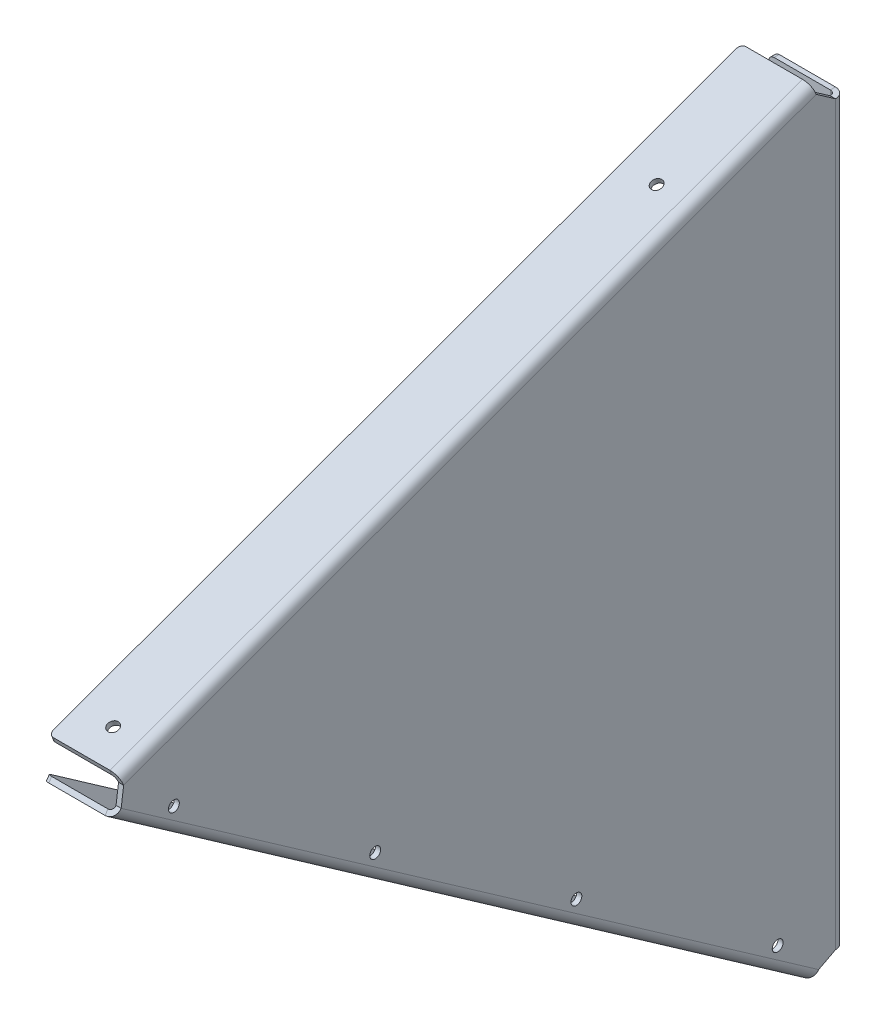
SolidWorks part; units mm, degrees
note: The reader was unsure of these and kept them because the rebuilt part matched: flange length of "Edge-Flange1".
ref_plane "Front Plane" through (0, 0, 0) normal (0, 0, 1) x (1, 0, 0)
ref_plane "Top Plane" through (0, 0, 0) normal (0, 1, 0) x (1, 0, 0)
ref_plane "Right Plane" through (0, 0, 0) normal (1, 0, 0) x (0, 0, -1)
sketch "Sketch1" plane through (0, 0, 0) normal (1, 0, 0) x (0, 0, -1)
  line L0 (0, 12.7) -> (0, 469.9)
  line L1 (-11.9341, 478.2563) -> (-441.5616, 321.8847)
  line L2 (-443.0924, 310.2567) -> (-10.4032, 7.2844)
  line L3 (-441.5616, 321.8847) -> (-443.0924, 310.2567)
  line L4 (0, 469.9) -> (-11.9341, 478.2563)
  line L5 (-10.4032, 7.2844) -> (0, 12.7)
  point P0 (0, 0)
  point P1 (0, 482.6)
  point P4 (-453.4957, 317.5411)
  dimension "D1" = 482.6
  dimension "D2" = 482.6
  dimension "D3" = 70
base flange "Base-Flange1" sketch "Sketch1" thickness 3.175 reverse thickness direction no parameters "D1"=2.032
edge flange "Edge-Flange1" sketch "Sketch16" flange profiles "Sketch16", "Sketch18", "Sketch20" flange angle 90 flange length 41.275 flange position bend outside bend radius 3.175 thickness 3.175 relief rectangular parameters "D6"=10, "D8"=1
bend "EdgeBend4" bend radius 3.175 bend angle 90 parameters "D5"=1
bend "EdgeBend5" bend radius 3.175 bend angle 90 parameters "D5"=2
bend "EdgeBend6" bend radius 3.175 bend angle 90 parameters "D5"=3
sketch "Sketch16" plane through (-3.175, 0, 0) normal (0, -0.8192, 0.5736) x (0, 0.5736, 0.8192)
  line L0 (540.916, 0) -> (12.7, 0) construction
  line L1 (540.916, 0) -> (12.7, 0)
  line L2 (12.7, 0) -> (12.7, 41.275)
  line L3 (12.7, 41.275) -> (540.916, 41.275)
  line L4 (540.916, 41.275) -> (540.916, 0)
sketch "Sketch18" plane through (-3.175, 0, 0) normal (0, 0, -1) x (0, -1, 0)
  line L0 (-12.7, 0) -> (-469.9, 0) construction
  line L1 (-12.7, 0) -> (-469.9, 0)
  line L2 (-469.9, 0) -> (-469.9, 41.275)
  line L3 (-469.9, 41.275) -> (-12.7, 41.275)
  line L4 (-12.7, 41.275) -> (-12.7, 0)
sketch "Sketch20" plane through (-3.175, 426.1465, 155.1047) normal (0, 0.9397, 0.342) x (0, 0.342, -0.9397)
  line L0 (152.3589, 0) -> (-304.8411, 0) construction
  line L1 (152.3589, 0) -> (-304.8411, 0)
  line L2 (-304.8411, 0) -> (-304.8411, 41.275)
  line L3 (-304.8411, 41.275) -> (152.3589, 41.275)
  line L4 (152.3589, 41.275) -> (152.3589, 0)
sketch "Sketch21" plane through (0, 0, -6.35) normal (0, 0, -1) x (-1, 0, 0)
  line L0 (44.45, 12.7) -> (44.45, 469.9) construction
  line L1 (6.35, 12.7) -> (44.45, 12.7) construction
  point P0 (22.225, 390.525)
  point P1 (22.225, 31.75)
  dimension "D1" = 22.225
  dimension "D2" = 358.775
  dimension "D3" = 19.05
hole_wizard "17/64 (0.26563) Diameter Hole1" positions "Sketch23" profile "Sketch24" hole size "17/64" standard "ANSI Inch"
sketch "Sketch23" plane through (0, 0, -6.35) normal (0, 0, -1) x (-1, 0, 0)
  point P0 (22.225, 390.525)
  point P3 (22.225, 31.75)
sketch "Sketch24" plane through (-22.225, 390.525, -6.35) normal (1, 0, 0) x (0, 1, 0)
  line L0 (0, 0) -> (0, 5.202)
  line L1 (0, 5.202) -> (3.3735, 3.175)
  line L2 (3.3735, 3.175) -> (3.3735, 0)
  line L5 (3.3735, 0) -> (0, 0)
  line L10 (0, 5.202) -> (-3.3735, 3.175) construction
  line L11 (0, -6.35) -> (0, 107.95) construction
  dimension "Hole Dia." = 6.747
  dimension "Hole Depth" = 3.175
  dimension "Drill Angle" = 118
sketch "Sketch26" plane through (0, 432.1136, 157.2765) normal (0, 0.9397, 0.342) x (1, 0, 0)
  line L0 (-44.45, 152.3589) -> (-44.45, -304.8411) construction
  line L1 (-44.45, -304.8411) -> (-6.35, -304.8411) construction
  point P0 (-22.225, -285.7911)
  point P1 (-22.225, 72.9839)
  dimension "D1" = 22.225
  dimension "D2" = 19.05
  dimension "D3" = 358.775
hole_wizard "17/64 (0.26563) Diameter Hole2" positions "Sketch27" profile "Sketch28" hole size "17/64" standard "ANSI Inch"
sketch "Sketch27" plane through (0, 432.1136, 157.2765) normal (0, 0.9397, 0.342) x (1, 0, 0)
  point P0 (-22.225, 72.9839)
  point P3 (-22.225, -285.7911)
sketch "Sketch28" plane through (-22.225, 457.0755, 88.694) normal (1, 0, 0) x (0, -0.342, 0.9397)
  line L0 (0, 0) -> (0, 5.202)
  line L1 (0, 5.202) -> (3.3735, 3.175)
  line L2 (3.3735, 3.175) -> (3.3735, 0)
  line L5 (3.3735, 0) -> (0, 0)
  line L10 (0, 5.202) -> (-3.3735, 3.175) construction
  line L11 (0, -6.35) -> (0, 107.95) construction
  dimension "Hole Dia." = 6.747
  dimension "Hole Depth" = 3.175
  dimension "Drill Angle" = 118
fillet "Fillet1" radius 3.175 6 edges at (-44.45, 306.3554, 445.8241) (-44.45, 326.36, 443.1904) (-44.45, 482.7316, 13.563) (-44.45, 469.9, -4.7625) (-44.45, 3.3832, 13.1349) (-44.45, 12.7, -4.7625)
sketch "Sketch30" plane through (0, -5.2016, 3.6422) normal (0, -0.8192, 0.5736) x (1, 0, 0)
  line L1 (-44.45, 537.741) -> (-44.45, 15.875) construction
  point P0 (-22.225, 505.408)
  point P1 (-22.225, 353.008)
  point P2 (-22.225, 200.608)
  point P3 (-22.225, 48.208)
  point P4 (-44.45, 276.808)
  dimension "D1" = 152.4
  dimension "D2" = 152.4
  dimension "D4" = 152.4
  dimension "D5" = 22.225
  dimension "D3" = 76.2
hole_wizard "17/64 (0.26563) Diameter Hole3" positions "Sketch31" profile "Sketch32" hole size "17/64" standard "ANSI Inch"
sketch "Sketch31" plane through (0, -5.2016, 3.6422) normal (0, -0.8192, 0.5736) x (-1, 0, 0)
  point P0 (22.225, -48.208)
  point P3 (22.225, -200.608)
  point P6 (22.225, -353.008)
  point P9 (22.225, -505.408)
sketch "Sketch32" plane through (-22.225, 22.4494, 43.1319) normal (1, 0, 0) x (0, -0.5736, -0.8192)
  line L0 (0, 0) -> (0, 5.202)
  line L1 (0, 5.202) -> (3.3735, 3.175)
  line L2 (3.3735, 3.175) -> (3.3735, 0)
  line L5 (3.3735, 0) -> (0, 0)
  line L10 (0, 5.202) -> (-3.3735, 3.175) construction
  line L11 (0, -6.35) -> (0, 107.95) construction
  dimension "Hole Dia." = 6.747
  dimension "Hole Depth" = 3.175
  dimension "Drill Angle" = 118
sketch "Sketch33" plane through (0, 0, 0) normal (1, 0, 0) x (0, 0, -1)
  line L0 (-410.3638, 295.0917) -> (-35.8475, 32.8526) construction
  line L1 (-443.0924, 310.2567) -> (-10.4032, 7.2844) construction
  line L2 (-446.7346, 305.055) -> (-14.0454, 2.0828) construction
  line L3 (-223.1056, 163.9722) -> (-230.39, 153.5689) construction
  point P2 (-160.6862, 120.2656)
  point P5 (-285.525, 207.6787)
  point P8 (-223.1056, 163.9722)
  point P9 (-230.39, 153.5689)
  dimension "D1" = 12.7
  dimension "D2" = 152.4
  dimension "D3" = 152.4
  dimension "D4" = 152.4
hole_wizard "17/64 (0.26563) Diameter Hole4" positions "Sketch34" profile "Sketch36" hole size "17/64" standard "ANSI Inch" end condition through all
sketch "Sketch34" plane through (0, 0, 0) normal (1, 0, 0) x (0, 0, -1)
  point P0 (-410.3638, 295.0917)
  point P3 (-285.525, 207.6787)
  point P6 (-160.6862, 120.2656)
  point P9 (-35.8475, 32.8526)
sketch "Sketch36" plane through (0, 295.0917, 410.3638) normal (0, 1, 0) x (0, 0, -1)
  line L0 (0, 0) -> (0, 44.45)
  line L1 (0, 44.45) -> (3.3735, 44.45)
  line L2 (3.3735, 44.45) -> (3.3735, 0)
  line L5 (3.3735, 0) -> (0, 0)
  line L11 (0, -6.35) -> (0, 107.95) construction
  dimension "Thru Hole Dia." = 6.747
  dimension "Thru Hole Depth" = 44.45
sketch "Bend-Lines1" [suppressed] plane through (0, 0, 0) normal (0, 1, 0) x (1, 0, 0)
sketch "Bounding-Box1" [suppressed] plane through (0, 0, 0) normal (0, 1, 0) x (1, 0, 0)
sheet metal parameters "Sheet-Metal1" thickness 3.175 parameters "D1"=2.032
flat pattern "Flat-Pattern1" [suppressed]
sketch "Bend-Lines2" plane through (0, 0, 0) normal (0, 1, 0) x (1, 0, 0)
sketch3d "Bounding-Box2" [suppressed]
  line L0 (-215.9, 644.525, 0) -> (212.725, 215.9, 0) construction
  line L1 (-430.2125, 430.2125, 0) -> (-1.5875, 1.5875, 0) construction
  line L2 (-215.9, 644.525, 0) -> (-430.2125, 430.2125, 0) construction
  line L3 (212.725, 215.9, 0) -> (-1.5875, 1.5875, 0) construction
sheet metal parameters "Sheet-Metal2" thickness 3.175 parameters "D1"=2.032
flat pattern "Flat-Pattern1" [suppressed]
sketch "Bend-Lines2" plane through (0, 0, 0) normal (1, 0, 0) x (0, 0, -1)
  line L6 (-4.0349, 485.3913) -> (-464.0571, 362.1287) construction
  line L7 (3.7405, 3.175) -> (3.7405, 479.425) construction
  line L8 (-465.914, 352.7936) -> (-4.7959, -1.0347) construction
  line L9 (-4.0349, 485.3913) -> (-464.0571, 362.1287) construction
  line L10 (3.7405, 3.175) -> (3.7405, 479.425) construction
  line L11 (-465.914, 352.7936) -> (-4.7959, -1.0347) construction
sketch3d "Bounding-Box2" [suppressed]
  line L0 (-244.8751, 702.2997, 0) -> (275.592, 302.9313, 0) construction
  line L1 (-521.0594, 342.3694, 0) -> (-0.5922, -56.999, 0) construction
  line L2 (-244.8751, 702.2997, 0) -> (-521.0594, 342.3694, 0) construction
  line L3 (275.592, 302.9313, 0) -> (-0.5922, -56.999, 0) construction
bend of the flat pattern "Flatten-<EdgeBend4>1"
bend of the flat pattern "Flatten-<EdgeBend5>1"
bend of the flat pattern "Flatten-<EdgeBend6>1"
sketch "Sketch21-1" [suppressed] plane through (0, 0, -1.1309) normal (1, 0, 0) x (0, 0, -1)
  line L0 (44.45, 3.175) -> (44.45, 479.425) construction
  line L1 (-1.1309, 3.175) -> (44.45, 3.175) construction
  point P0 (22.225, 447.675)
  point P1 (22.225, 41.275)
  dimension "D1" = 22.225
  dimension "D2" = 406.4
  dimension "D3" = 38.1
sheet metal parameters "Sheet-Metal3" thickness 3.175 parameters "D1"=2.032
flat pattern "Flat-Pattern1" [suppressed]
sketch "Bend-Lines2" plane through (0, 0, 0) normal (1, 0, 0) x (0, 0, -1)
  line L6 (-4.0349, 485.3913) -> (-464.0571, 362.1287) construction
  line L7 (3.7405, 3.175) -> (3.7405, 479.425) construction
  line L8 (-465.914, 352.7936) -> (-4.7959, -1.0347) construction
  line L9 (-4.0349, 485.3913) -> (-464.0571, 362.1287) construction
  line L10 (3.7405, 3.175) -> (3.7405, 479.425) construction
  line L11 (-465.914, 352.7936) -> (-4.7959, -1.0347) construction
sketch3d "Bounding-Box2" [suppressed]
  line L0 (-244.8751, 702.2997, 0) -> (275.592, 302.9313, 0) construction
  line L1 (-521.0594, 342.3694, 0) -> (-0.5922, -56.999, 0) construction
  line L2 (-244.8751, 702.2997, 0) -> (-521.0594, 342.3694, 0) construction
  line L3 (275.592, 302.9313, 0) -> (-0.5922, -56.999, 0) construction
bend of the flat pattern "Flatten-<EdgeBend4>1"
bend of the flat pattern "Flatten-<EdgeBend5>1"
bend of the flat pattern "Flatten-<EdgeBend6>1"
sketch "Sketch21-1" [suppressed] plane through (0, 0, -1.1309) normal (1, 0, 0) x (0, 0, -1)
  line L0 (44.45, 3.175) -> (44.45, 479.425) construction
  line L1 (-1.1309, 3.175) -> (44.45, 3.175) construction
  point P0 (22.225, 400.05)
  point P1 (22.225, 41.275)
  dimension "D1" = 22.225
  dimension "D2" = 358.775
  dimension "D3" = 38.1
sheet metal parameters "Sheet-Metal4" thickness 3.175 parameters "D1"=2.032
flat pattern "Flat-Pattern1" [suppressed]
sketch "Bend-Lines2" plane through (0, 0, 0) normal (1, 0, 0) x (0, 0, -1)
  line L6 (-4.0349, 485.3913) -> (-464.0571, 362.1287) construction
  line L7 (3.7405, 3.175) -> (3.7405, 479.425) construction
  line L8 (-465.914, 352.7936) -> (-4.7959, -1.0347) construction
  line L9 (-4.0349, 485.3913) -> (-464.0571, 362.1287) construction
  line L10 (3.7405, 3.175) -> (3.7405, 479.425) construction
  line L11 (-465.914, 352.7936) -> (-4.7959, -1.0347) construction
sketch3d "Bounding-Box2" [suppressed]
  line L0 (-244.6392, 700.5096, 0) -> (273.8019, 302.6955, 0) construction
  line L1 (-520.0463, 341.5923, 0) -> (-1.6052, -56.2218, 0) construction
  line L2 (-244.6392, 700.5096, 0) -> (-520.0463, 341.5923, 0) construction
  line L3 (273.8019, 302.6955, 0) -> (-1.6052, -56.2218, 0) construction
bend of the flat pattern "Flatten-<EdgeBend4>1"
bend of the flat pattern "Flatten-<EdgeBend5>1"
bend of the flat pattern "Flatten-<EdgeBend6>1"
sketch "Sketch21-1" plane through (0, 0, -1.1309) normal (1, 0, 0) x (0, 0, -1)
  line L0 (44.45, 6.35) -> (44.45, 476.25) construction
  line L1 (-1.1309, 3.175) -> (41.275, 3.175) construction
  point P0 (22.225, 390.525)
  point P1 (22.225, 31.75)
  dimension "D1" = 22.225
  dimension "D2" = 358.775
  dimension "D3" = 28.575
sketch "Sketch26-1" [suppressed] plane through (0, 451.3643, 120.9427) normal (1, 0, 0) x (0, -0.9659, -0.2588)
  line L0 (-44.45, 118.5561) -> (-44.45, -351.3439) construction
  line L1 (-41.275, -354.5189) -> (1.1309, -354.5189) construction
  point P0 (-22.225, -325.9439)
  point P1 (-22.225, 32.8311)
  dimension "D1" = 22.225
  dimension "D2" = 28.575
  dimension "D3" = 358.775
sheet metal parameters "Sheet-Metal5" thickness 3.175 parameters "D1"=2.032
flat pattern "Flat-Pattern1" [suppressed]
sketch "Bend-Lines2" plane through (0, 0, 0) normal (1, 0, 0) x (0, 0, -1)
  line L6 (-13.2134, 481.7712) -> (-442.8409, 325.3996) construction
  line L7 (3.7405, 12.7) -> (3.7405, 469.9) construction
  line L8 (-445.2379, 307.1927) -> (-12.5487, 4.2204) construction
  line L9 (-13.2134, 481.7712) -> (-442.8409, 325.3996) construction
  line L10 (3.7405, 12.7) -> (3.7405, 469.9) construction
  line L11 (-445.2379, 307.1927) -> (-12.5487, 4.2204) construction
sketch3d "Bounding-Box2" [suppressed]
  line L0 (-242.03, 669.7656, 0) -> (258.6579, 319.1783, 0) construction
  line L1 (-503.2365, 296.7261, 0) -> (-2.5487, -53.8612, 0) construction
  line L2 (-242.03, 669.7656, 0) -> (-503.2365, 296.7261, 0) construction
  line L3 (258.6579, 319.1783, 0) -> (-2.5487, -53.8612, 0) construction
bend of the flat pattern "Flatten-<EdgeBend4>1"
bend of the flat pattern "Flatten-<EdgeBend5>1"
bend of the flat pattern "Flatten-<EdgeBend6>1"
sketch "Sketch21-1" plane through (0, 0, -1.1309) normal (1, 0, 0) x (0, 0, -1)
  line L0 (44.45, 15.875) -> (44.45, 466.725) construction
  line L1 (-1.1309, 12.7) -> (41.275, 12.7) construction
  point P0 (22.225, 390.525)
  point P1 (22.225, 31.75)
  dimension "D1" = 22.225
  dimension "D2" = 358.775
  dimension "D3" = 19.05
sketch "Sketch26-1" plane through (0, 427.2092, 155.4914) normal (1, 0, 0) x (0, -0.9397, -0.342)
  line L0 (-44.45, 149.1839) -> (-44.45, -301.6661) construction
  line L1 (-41.275, -304.8411) -> (1.1309, -304.8411) construction
  point P0 (-22.225, -285.7911)
  point P1 (-22.225, 72.9839)
  dimension "D1" = 22.225
  dimension "D2" = 19.05
  dimension "D3" = 358.775
sketch "Sketch30-1" plane through (0, -0.9264, 0.6487) normal (1, 0, 0) x (0, 0.8192, -0.5736)
  line L1 (-44.45, 537.741) -> (-44.45, 15.875) construction
  point P0 (-22.225, 505.408)
  point P1 (-22.225, 353.008)
  point P2 (-22.225, 200.608)
  point P3 (-22.225, 48.208)
  point P4 (-44.45, 276.808)
  dimension "D1" = 152.4
  dimension "D2" = 152.4
  dimension "D3" = 76.2
  dimension "D4" = 152.4
  dimension "D5" = 22.225
sheet metal parameters "Sheet-Metal6" thickness 3.175 parameters "D1"=2.032
flat pattern "Flat-Pattern1" [suppressed]
sketch "Bend-Lines2" plane through (0, 0, 0) normal (1, 0, 0) x (0, 0, -1)
  line L6 (-13.2134, 481.7712) -> (-442.8409, 325.3996) construction
  line L7 (3.7405, 12.7) -> (3.7405, 469.9) construction
  line L8 (-445.2379, 307.1927) -> (-12.5487, 4.2204) construction
  line L9 (-13.2134, 481.7712) -> (-442.8409, 325.3996) construction
  line L10 (3.7405, 12.7) -> (3.7405, 469.9) construction
  line L11 (-445.2379, 307.1927) -> (-12.5487, 4.2204) construction
sketch3d "Bounding-Box2" [suppressed]
  line L0 (-242.03, 669.7656, 0) -> (258.6579, 319.1783, 0) construction
  line L1 (-503.2365, 296.7261, 0) -> (-2.5487, -53.8612, 0) construction
  line L2 (-242.03, 669.7656, 0) -> (-503.2365, 296.7261, 0) construction
  line L3 (258.6579, 319.1783, 0) -> (-2.5487, -53.8612, 0) construction
bend of the flat pattern "Flatten-<EdgeBend4>1"
bend of the flat pattern "Flatten-<EdgeBend5>1"
bend of the flat pattern "Flatten-<EdgeBend6>1"
sketch "Sketch21-1" plane through (0, 0, -1.1309) normal (1, 0, 0) x (0, 0, -1)
  line L0 (44.45, 15.875) -> (44.45, 466.725) construction
  line L1 (-1.1309, 12.7) -> (41.275, 12.7) construction
  point P0 (22.225, 390.525)
  point P1 (22.225, 31.75)
  dimension "D1" = 22.225
  dimension "D2" = 358.775
  dimension "D3" = 19.05
sketch "Sketch26-1" plane through (0, 427.2092, 155.4914) normal (1, 0, 0) x (0, -0.9397, -0.342)
  line L0 (-44.45, 149.1839) -> (-44.45, -301.6661) construction
  line L1 (-41.275, -304.8411) -> (1.1309, -304.8411) construction
  point P0 (-22.225, -285.7911)
  point P1 (-22.225, 72.9839)
  dimension "D1" = 22.225
  dimension "D2" = 19.05
  dimension "D3" = 358.775
sketch "Sketch30-1" plane through (0, -0.9264, 0.6487) normal (1, 0, 0) x (0, 0.8192, -0.5736)
  line L1 (-44.45, 537.741) -> (-44.45, 15.875) construction
  point P0 (-22.225, 505.408)
  point P1 (-22.225, 353.008)
  point P2 (-22.225, 200.608)
  point P3 (-22.225, 48.208)
  point P4 (-44.45, 276.808)
  dimension "D1" = 152.4
  dimension "D2" = 152.4
  dimension "D3" = 76.2
  dimension "D4" = 152.4
  dimension "D5" = 22.225
equation "\"D2@Sketch1\"=\"D1@Sketch1\""
equation "\"D3@Sketch30\"=\"D4@Sketch30\"/2"
